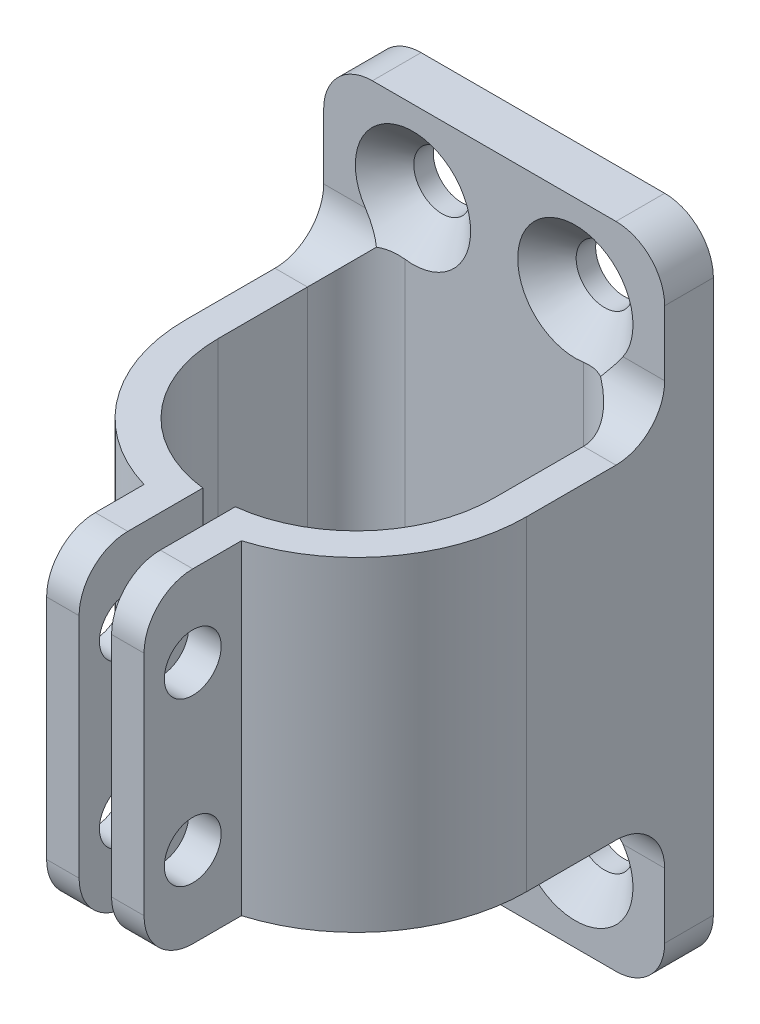
SolidWorks part; units mm, degrees
ref_plane "Front Plane" through (0, 0, 0) normal (0, 0, 1) x (1, 0, 0)
ref_plane "Top Plane" through (0, 0, 0) normal (0, 1, 0) x (1, 0, 0)
ref_plane "Right Plane" through (0, 0, 0) normal (1, 0, 0) x (0, 0, -1)
sketch "Sketch1" plane through (0, 0, 0) normal (0, 0, 1) x (1, 0, 0)
  line L1 (-10.5, 20) -> (10.5, 20)
  line L2 (-10.5, 20) -> (-10.5, -20)
  line L3 (-10.5, -20) -> (10.5, -20)
  line L4 (10.5, 20) -> (10.5, -20)
  line L5 (-10.5, 20) -> (10.5, -20) construction
  line L6 (-10.5, -20) -> (10.5, 20) construction
  line L7 (-5, 15) -> (5, 15) construction
  line L8 (-5, 15) -> (-5, -15) construction
  line L9 (-5, -15) -> (5, -15) construction
  line L10 (5, 15) -> (5, -15) construction
  line L11 (-5, 15) -> (5, -15) construction
  line L12 (-5, -15) -> (5, 15) construction
  circle A0 centre (-5, 15) radius 1.75
  circle A1 centre (5, 15) radius 1.75
  circle A2 centre (5, -15) radius 1.75
  circle A3 centre (-5, -15) radius 1.75
  point P0 (0, 0)
  point P5 (0, 0)
  dimension "D1" = 3.5
  dimension "D2" = 10
  dimension "D3" = 30
  dimension "D4" = 5
  dimension "D5" = 21
extrude "Boss-Extrude1" add sketch "Sketch1" along normal blind 3
sketch "Sketch3" plane through (0, 0, 0) normal (0, 1, 0) x (1, 0, 0)
  line L0 (10.5, -3) -> (-10.5, -3) construction
  line L10 (-8.5, -3) -> (-8.5, -11.5)
  line L25 (-27.6265, -787.8792) -> (29.8019, -2.8849) construction
  line L26 (-24.1749, -713.2878) -> (27.6541, -4.8322) construction
  line L27 (10.5004, -4.4068) -> (27.6541, -4.8322) construction
  line L28 (-10.5, -10.4105) -> (-24.1749, -713.2878) construction
  line L29 (-11.6968, 30.8925) -> (-27.6265, -787.8792) construction
  line L30 (10.5463, -2.4073) -> (29.8019, -2.8849) construction
  line L33 (-10.5, -10.4105) -> (-10.5, -10.4105) construction
  line L37 (-3, -21.5623) -> (-3, -27.5623)
  line L38 (-3, -27.5623) -> (-1, -27.5623)
  line L41 (-1, -27.5623) -> (-1, -19.941)
  line L44 (-11.6968, 30.8925) -> (-8.5, -3) construction
  line L46 (-10.5, -3) -> (-8.5, -3)
  line L48 (8.4285, -2.3627) -> (10.5463, -2.4073) construction
  line L49 (0, 0) -> (0, -27.5623) construction
  line L50 (8.4285, -2.3627) -> (0.8972, -3.0475) construction
  line L51 (8.4982, -4.3646) -> (7.7643, -4.4313) construction
  line L52 (8.4982, -4.3646) -> (10.5004, -4.4068) construction
  line L53 (10.5, 0) -> (-10.5, 0) construction
  line L54 (-10.5, -10.4105) -> (-10.5, -11.5) construction
  line L55 (-10.5, -11.5) -> (-10.5, -3)
  line L56 (10.5, -11.5) -> (10.5, -3)
  line L57 (10.5, -3) -> (8.5, -3)
  line L58 (1, -27.5623) -> (1, -19.941)
  line L59 (3, -27.5623) -> (1, -27.5623)
  line L60 (3, -21.5623) -> (3, -27.5623)
  line L61 (8.5, -3) -> (8.5, -11.5)
  arc A0 (-8.5, -11.5) -> (-1, -19.941) centre (0, -11.5) ccw
  arc A1 (-10.5, -11.5) -> (-3, -21.5623) centre (0, -11.5) ccw
  arc A3 (-10.5, -11.5) -> (7.7643, -4.4313) centre (0, -11.5) ccw construction
  arc A6 (-8.5, -11.5) -> (0.8972, -3.0475) centre (0, -11.5) ccw construction
  arc A7 (10.5, -11.5) -> (3, -21.5623) centre (0, -11.5) cw
  arc A8 (8.5, -11.5) -> (1, -19.941) centre (0, -11.5) cw
  dimension "D1" = 17
  dimension "D2" = 2
  dimension "D3" = 2
  dimension "D4" = 6
  dimension "D5" = 1
extrude "Boss-Extrude2" add sketch "Sketch3" against normal mid plane 20
sketch "Sketch4" plane through (3, 0, 0) normal (1, 0, 0) x (0, 0, -1)
  line L0 (-24.5623, 10) -> (-24.5623, -10) construction
  line L9 (-27.5623, 0) -> (-27.5623, 10) construction
  line L10 (-27.5623, 0) -> (-27.5623, -10) construction
  line L12 (-21.5623, -10) -> (-27.5623, -10) construction
  line L13 (-27.5623, 10) -> (-21.5623, 10) construction
  line L14 (-27.5623, -10) -> (-27.5623, 10) construction
  circle A0 centre (-24.5623, 5) radius 1.75
  circle A1 centre (-24.5623, -5) radius 1.75
  point P23 (-27.5623, 5)
  point P28 (-27.5623, -5)
  dimension "D1" = 3.5
  dimension "D2" = 3.5
extrude "Cut-Extrude1" cut sketch "Sketch4" against normal through all both and the other way through all
chamfer "Chamfer1" distance 1.8 angle 45 4 edges at (6.75, -15, 3) (-3.25, -15, 3) (6.75, 15, 3) (-3.25, 15, 3)
fillet "Fillet1" radius 3 8 edges at (-10.5, 20, 1.5) (-10.5, -20, 1.5) (10.5, -20, 1.5) (10.5, 20, 1.5) (2, -10, 27.5623) (-2, -10, 27.5623) (-2, 10, 27.5623) (2, 10, 27.5623)
fillet "Fillet2" radius 3 4 edges at (9.5, -10, 3) (-9.5, -10, 3) (9.5, 10, 3) (-9.5, 10, 3)
fillet "Fillet3" radius 3 2 edges at (8.5, 0, 3) (-8.5, 0, 3)
